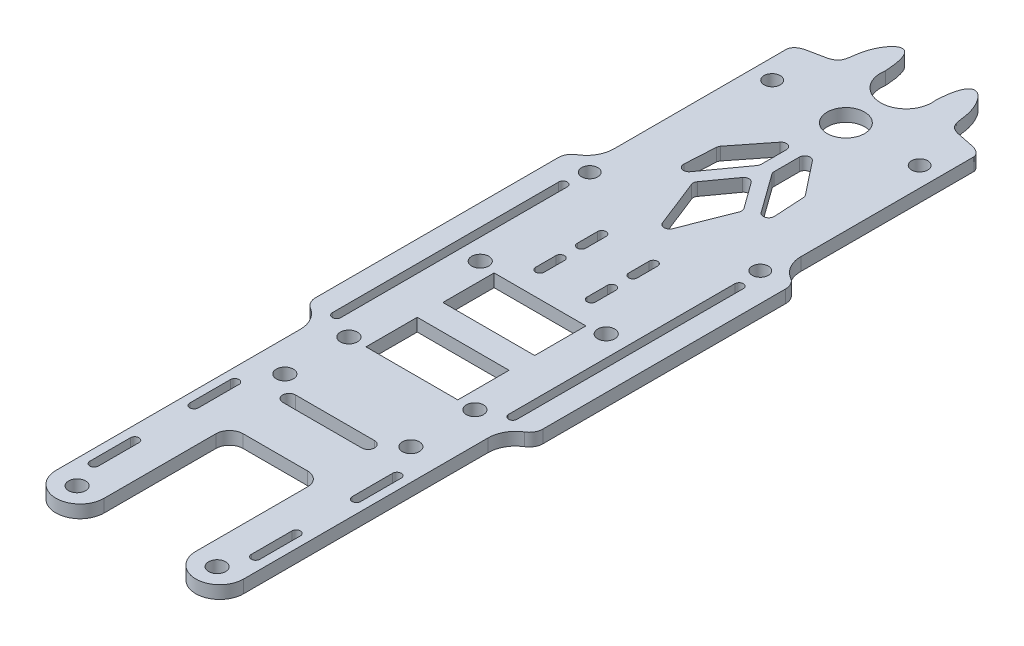
SolidWorks part; units mm, degrees
ref_plane "Front Plane" through (0, 0, 0) normal (0, 0, 1) x (1, 0, 0)
ref_plane "Top Plane" through (0, 0, 0) normal (0, 1, 0) x (1, 0, 0)
ref_plane "Right Plane" through (0, 0, 0) normal (1, 0, 0) x (0, 0, -1)
sketch "Sketch1" plane through (0, 0, 0) normal (0, 1, 0) x (1, 0, 0)
  line L1 (9.5179, -5.1674) -> (51.7851, -5.1674)
  line L2 (9.5179, -5.1674) -> (9.5179, 43.2514)
  line L3 (9.5179, 43.2514) -> (51.7851, 43.2514)
  line L4 (51.7851, -5.1674) -> (51.7851, 43.2514)
  line L5 (13.2882, 43.2514) -> (48.0148, 43.2514)
  line L6 (13.2882, 43.2514) -> (13.2882, 80.3592)
  line L8 (48.0148, 43.2514) -> (48.0148, 80.3592)
  line L9 (22.1187, -6.7549) -> (39.1843, -6.7549)
  line L10 (13.189, -5.1674) -> (48.114, -5.1674)
  line L11 (13.189, -5.1674) -> (13.189, -59.9361)
  line L12 (13.189, -59.9361) -> (22.1533, -59.9361)
  line L13 (48.114, -5.1674) -> (48.114, -59.9361)
  line L14 (22.1187, -6.7549) -> (22.1187, 2.7701)
  line L15 (22.1187, 2.7701) -> (39.1843, 2.7701)
  line L16 (39.1843, -6.7549) -> (39.1843, 2.7701)
  line L20 (35.4351, 21.8201) -> (35.4351, 25.5901) construction
  line L21 (23.3093, -22.233) -> (37.9937, -22.233) construction
  line L22 (34.6413, 21.8201) -> (34.6413, 25.5901)
  line L23 (36.2288, 21.8201) -> (36.2288, 25.5901)
  line L24 (47.0226, -4.3736) -> (47.0226, 37.6951) construction
  line L25 (23.3093, -21.0424) -> (37.9937, -21.0424)
  line L26 (23.3093, -23.4236) -> (37.9937, -23.4236)
  line L27 (22.1187, 7.5326) -> (39.1843, 7.5326)
  line L28 (46.2288, -4.3736) -> (46.2288, 37.6951)
  line L29 (47.8163, -4.3736) -> (47.8163, 37.6951)
  line L30 (22.1187, 7.5326) -> (22.1187, 17.0576)
  line L31 (22.1187, 17.0576) -> (39.1843, 17.0576)
  line L32 (39.1843, 7.5326) -> (39.1843, 17.0576)
  line L33 (45.7327, -32.1549) -> (45.7327, -24.6143) construction
  line L34 (30.6515, 80.3592) -> (30.6515, -32.1549)
  line L35 (44.939, -32.1549) -> (44.939, -24.6143)
  line L36 (46.5265, -32.1549) -> (46.5265, -24.6143)
  line L37 (35.4351, 29.5588) -> (35.4351, 33.3287) construction
  line L38 (34.6413, 29.5588) -> (34.6413, 33.3287)
  line L39 (36.2288, 29.5588) -> (36.2288, 33.3287)
  line L40 (25.8679, 29.5588) -> (25.8679, 33.3287) construction
  line L41 (26.6616, 29.5588) -> (26.6616, 33.3287)
  line L42 (25.0741, 29.5588) -> (25.0741, 33.3287)
  line L43 (25.8679, 21.8201) -> (25.8679, 25.5901) construction
  line L44 (26.6616, 21.8201) -> (26.6616, 25.5901)
  line L45 (25.0741, 21.8201) -> (25.0741, 25.5901)
  line L46 (14.2804, -4.3736) -> (14.2804, 37.6951) construction
  line L47 (15.0741, -4.3736) -> (15.0741, 37.6951)
  line L48 (13.4866, -4.3736) -> (13.4866, 37.6951)
  line L49 (15.5702, -32.1549) -> (15.5702, -24.6143) construction
  line L50 (16.364, -32.1549) -> (16.364, -24.6143)
  line L51 (14.7765, -32.1549) -> (14.7765, -24.6143)
  line L52 (22.1533, -32.1549) -> (39.2189, -32.1549)
  line L53 (39.2189, -32.1549) -> (39.2189, -59.9361)
  line L54 (22.1533, -32.1549) -> (22.1533, -59.9361)
  line L55 (45.6547, -50.808) -> (45.6547, -43.2674) construction
  line L56 (44.861, -50.808) -> (44.861, -43.2674)
  line L57 (46.4485, -50.808) -> (46.4485, -43.2674)
  line L58 (39.2189, -59.9361) -> (48.114, -59.9361)
  line L59 (30.6515, 56.6234) -> (35.2967, 50.1871)
  line L60 (35.2967, 50.1871) -> (30.6515, 38.3671)
  line L61 (31.8421, 66.9801) -> (31.8421, 59.0426)
  line L62 (31.8421, 59.0426) -> (39.2745, 48.7446)
  line L63 (39.2745, 48.7446) -> (38.7221, 58.2536)
  line L64 (38.7221, 58.2536) -> (31.8421, 66.9801)
  line L65 (15.6483, -50.808) -> (15.6483, -43.2674) construction
  line L66 (16.442, -50.808) -> (16.442, -43.2674)
  line L67 (14.8545, -50.808) -> (14.8545, -43.2674)
  line L68 (26.0063, 50.1871) -> (30.6515, 38.3671)
  line L69 (30.6515, 56.6234) -> (26.0063, 50.1871)
  line L70 (22.0285, 48.7446) -> (22.5809, 58.2536)
  line L71 (29.4609, 59.0426) -> (22.0285, 48.7446)
  line L72 (29.4609, 66.9801) -> (29.4609, 59.0426)
  line L73 (22.5809, 58.2536) -> (29.4609, 66.9801)
  circle A0 centre (42.3593, -6.7549) radius 1.5875
  arc A1 (34.6413, 21.8201) -> (36.2288, 21.8201) centre (35.4351, 21.8201) ccw
  arc A2 (36.2288, 25.5901) -> (34.6413, 25.5901) centre (35.4351, 25.5901) ccw
  arc A3 (23.3093, -21.0424) -> (23.3093, -23.4236) centre (23.3093, -22.233) ccw
  arc A4 (37.9937, -23.4236) -> (37.9937, -21.0424) centre (37.9937, -22.233) ccw
  arc A5 (46.2288, -4.3736) -> (47.8163, -4.3736) centre (47.0226, -4.3736) ccw
  arc A6 (47.8163, 37.6951) -> (46.2288, 37.6951) centre (47.0226, 37.6951) ccw
  arc A7 (44.939, -32.1549) -> (46.5265, -32.1549) centre (45.7327, -32.1549) ccw
  arc A8 (46.5265, -24.6143) -> (44.939, -24.6143) centre (45.7327, -24.6143) ccw
  arc A9 (34.6413, 29.5588) -> (36.2288, 29.5588) centre (35.4351, 29.5588) ccw
  arc A10 (36.2288, 33.3287) -> (34.6413, 33.3287) centre (35.4351, 33.3287) ccw
  circle A11 centre (42.3593, 17.6529) radius 1.5875
  circle A12 centre (42.3593, -18.6611) radius 1.5875
  arc A13 (26.6616, 29.5588) -> (25.0741, 29.5588) centre (25.8679, 29.5588) cw
  arc A14 (25.0741, 33.3287) -> (26.6616, 33.3287) centre (25.8679, 33.3287) cw
  arc A15 (26.6616, 21.8201) -> (25.0741, 21.8201) centre (25.8679, 21.8201) cw
  arc A16 (25.0741, 25.5901) -> (26.6616, 25.5901) centre (25.8679, 25.5901) cw
  circle A17 centre (18.9437, 17.6529) radius 1.5875
  arc A18 (15.0741, -4.3736) -> (13.4866, -4.3736) centre (14.2804, -4.3736) cw
  arc A19 (13.4866, 37.6951) -> (15.0741, 37.6951) centre (14.2804, 37.6951) cw
  circle A20 centre (18.9437, -6.7549) radius 1.5875
  circle A21 centre (18.9437, -18.6611) radius 1.5875
  arc A22 (16.364, -32.1549) -> (14.7765, -32.1549) centre (15.5702, -32.1549) cw
  arc A23 (14.7765, -24.6143) -> (16.364, -24.6143) centre (15.5702, -24.6143) cw
  circle A24 centre (46.5048, 42.1456) radius 1.504
  circle A25 centre (30.6515, 73.91) radius 3.4727
  circle A26 centre (44.3594, 73.91) radius 1.504
  arc A27 (44.861, -50.808) -> (46.4485, -50.808) centre (45.6547, -50.808) ccw
  arc A28 (46.4485, -43.2674) -> (44.861, -43.2674) centre (45.6547, -43.2674) ccw
  circle A29 centre (43.6665, -55.9674) radius 1.5875
  circle A30 centre (17.6365, -55.9674) radius 1.5875
  arc A31 (16.442, -50.808) -> (14.8545, -50.808) centre (15.6483, -50.808) cw
  arc A32 (14.8545, -43.2674) -> (16.442, -43.2674) centre (15.6483, -43.2674) cw
  circle A33 centre (14.7982, 42.1456) radius 1.504
  circle A34 centre (16.9436, 73.91) radius 1.504
  circle A35 centre (30.6515, 85.1217) radius 4.7625
  spline S0 degree 3 poles (35.3427, 85.9429) (35.8139, 94.7404) (40.9626, 89.3168) (40.6952, 81.322) (47.5188, 82.7553) (48.0148, 80.3592) knots 0 0 0 0 0.509252 0.660799 1 1 1 1
  spline S1 degree 3 poles (25.9603, 85.9429) (25.4891, 94.7404) (20.3404, 89.3168) (20.6077, 81.322) (13.7842, 82.7553) (13.2882, 80.3592) knots 0 0 0 0 0.509252 0.660799 1 1 1 1
  point P8 (30.6515, 43.2514)
  point P9 (30.6515, -5.1674)
  point P18 (22.1187, -22.233)
  point P21 (36.2288, 23.7051)
  point P24 (35.4351, 23.7051)
  point P32 (30.6515, -22.233)
  point P39 (30.6515, -6.7549)
  point P40 (47.0226, 16.6607)
  point P46 (45.7327, -28.3846)
  point P53 (35.4351, 21.0264)
  point P64 (35.4351, 31.4438)
  point P72 (35.4351, 28.7651)
  point P73 (35.4351, 26.3838)
  point P77 (45.6547, -47.0377)
  point P83 (39.1843, -22.233)
  point P86 (25.8679, 31.4438)
  point P93 (25.8679, 23.7051)
  point P102 (14.2804, 16.6607)
  point P113 (15.5702, -28.3846)
  point P126 (43.6665, -59.9361)
  point P137 (15.6483, -47.0377)
  point P155 (41.688, 85.6065)
  point P157 (44.3594, 82.2681)
  point P159 (36.9418, 90.956)
  point P161 (39.2745, 86.8534)
  point P162 (44.3594, 82.8597)
  point P163 (35.2967, 87.5372)
  point P164 (0, 0)
  point P165 (35.2967, 86.8689)
  point P166 (37.9937, 89.4678)
  point P167 (45.7327, 80.3592)
  point P168 (40.964, 84.0781)
  point P169 (36.2288, 90.4678)
  point P170 (40.5869, 86.4644)
  point P171 (39.8362, 82.044)
  point P172 (0, 0)
  point P173 (41.0039, 83.8789)
  point P174 (43.6665, 82.461)
  point P175 (0, 0)
  point P176 (37.9937, 90.9682)
  point P177 (0, 0)
  point P178 (0, 0)
  point P179 (40.1924, 82.6642)
  point P180 (0, 0)
  point P181 (0, 0)
  point P182 (40.7018, 83.7572)
  point P183 (0, 0)
  point P184 (0, 0)
  point P185 (43.6665, 82.3907)
  point P186 (0, 0)
  point P187 (0, 0)
  point P188 (41.4086, 83.3331)
  dimension "D9" = 3.175
  dimension "D11" = 1.5875
  dimension "D13" = 17.0656
  dimension "D10" = 3.7699
  dimension "D20" = 3.9688
  dimension "D25" = 1.1906
  dimension "D27" = 21.2328
  dimension "D28" = 8.7312
  dimension "D29" = 3.0079
  dimension "D30" = 2.1828
  dimension "D31" = 6.9453
  dimension "D33" = 8.7312
  dimension "D34" = 9.525
  dimension "D35" = 3.175
  dimension "D49" = 9.525
  dimension "D1" = 48.4187
  dimension "D2" = 42.2672
  dimension "D3" = 37.1078
  dimension "D4" = 34.7266
  dimension "D5" = 54.7687
  dimension "D6" = 34.925
  dimension "D7" = 9.525
  dimension "D8" = 17.0656
  dimension "D12" = 2.3813
  dimension "D14" = 1.5875
  dimension "D15" = 42.0687
  dimension "D16" = 3.9688
  dimension "D17" = 3.175
  dimension "D18" = 14.2875
  dimension "D19" = 4.7625
  dimension "D21" = 10
  dimension "D22" = 1.5875
  dimension "D23" = 1.5875
  dimension "D24" = 17.0656
  dimension "D26" = 2.3813
  dimension "D36" = 2.3813
  dimension "D37" = 7.5406
  dimension "D38" = 8.9643
  dimension "D39" = 12.7
  dimension "D40" = 7.9375
  dimension "D41" = 18.2562
  dimension "D42" = 5.5562
  dimension "D43" = 1.1906
  dimension "D44" = 2.3813
  dimension "D45" = 11.1125
  dimension "D46" = 9.525
  dimension "D47" = 12.7
  dimension "D48" = 7.9375
extrude "Boss-Extrude2" add sketch "Sketch1" along normal mid plane 2.3813 contours L1 A20 L10 L11 L12 L34 L26 A3 L25 L9 L14 A21 L51 A23 L50 A22 | A4 L26 L34 L12 L13 L1 L10 A0 L16 L9 L25 A12 A8 L36 A7 L35 | L48 A19 L47 A18 L10 L1 L14 L15 L34 L27 L30 L31 L3 L2 L45 A16 L44 A15 L42 A14 L41 A13 A17 | A6 L29 A5 L1 L4 L3 L5 L34 L31 L32 L27 L15 L16 L10 L28 A11 A10 L39 A9 L38 A2 L23 A1 L22 | L34 L6 L3 | L34 L5 L8 region at (19.2609, 0, -21.2507) region at (20.422, 0, 28.4012) region at (21.0194, 0, -65.0923) region at (40.8861, 0, 28.3476) region at (40.2836, 0, -65.0932) region at (42.0421, 0, -21.2507)
fillet "Fillet1" radius 5.08 4 edges at (13.2882, 0, -43.2514) (48.0148, 0, -43.2514) (48.114, 0, 5.1674) (13.189, 0, 5.1674)
fillet "Fillet2" radius 2.54 6 edges at (9.5179, 0, 5.1674) (9.5179, 0, -43.2514) (51.7851, 0, -43.2514) (51.7851, 0, 5.1674) (39.2189, 0, 32.1549) (22.1533, 0, 32.1549)
fillet "Fillet5" radius 1.016 12 edges at (29.4609, 0, -59.0426) (22.0285, 0, -48.7446) (22.5809, 0, -58.2536) (29.4609, 0, -66.9801) (30.6515, 0, -38.3671) (35.2967, 0, -50.1871) (26.0063, 0, -50.1871) (30.6515, 0, -56.6234) (39.2745, 0, -48.7446) (38.7221, 0, -58.2536) (31.8421, 0, -59.0426) (31.8421, 0, -66.9801)
fillet "Fillet12" 2 edges at (13.189, 0, 59.9361) (22.1533, 0, 59.9361) type full round first side face at (13.189, 0, 34.9921) second side face at (22.1533, 0, 47.3155) middle face at (17.6712, 0, 59.9361)
fillet "Fillet13" 2 edges at (48.114, 0, 59.9361) (39.2189, 0, 59.9361) type full round first side face at (48.114, 0, 34.9921) second side face at (39.2189, 0, 47.3155) middle face at (43.6665, 0, 59.9361)
